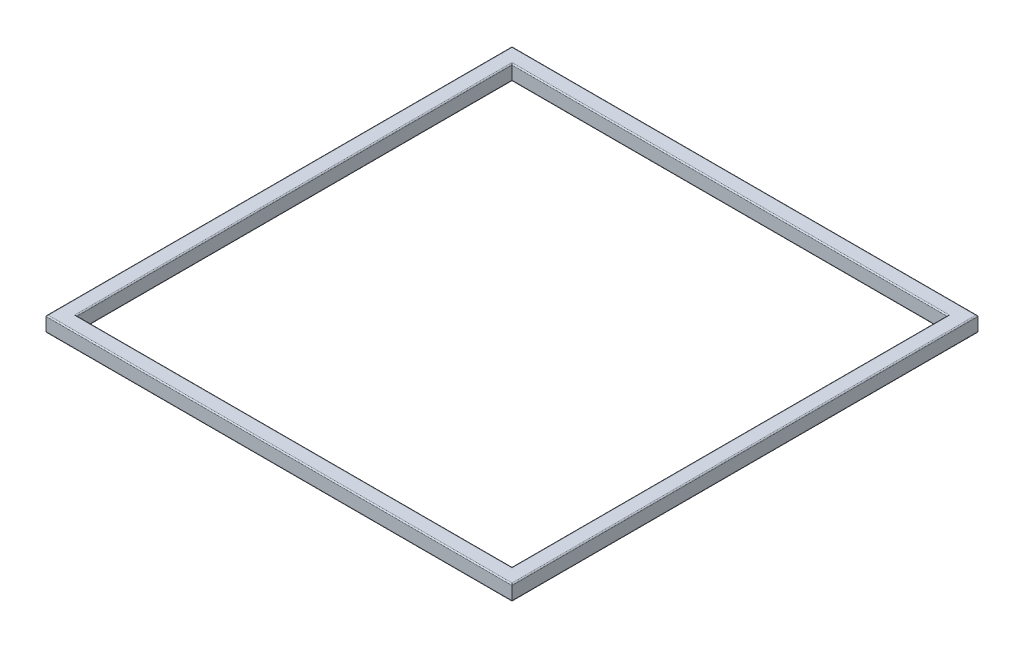
SolidWorks part; units mm, degrees
ref_plane "Front Plane" through (0, 0, 0) normal (0, 0, 1) x (1, 0, 0)
ref_plane "Top Plane" through (0, 0, 0) normal (0, 1, 0) x (1, 0, 0)
ref_plane "Right Plane" through (0, 0, 0) normal (1, 0, 0) x (0, 0, -1)
sketch "Sketch1" plane through (0, 0, 0) normal (0, 1, 0) x (1, 0, 0)
  line L1 (-610, 610) -> (610, 610)
  line L2 (-610, 610) -> (-610, -610)
  line L3 (-610, -610) -> (610, -610)
  line L4 (610, 610) -> (610, -610)
  line L5 (-610, 610) -> (610, -610) construction
  line L6 (-610, -610) -> (610, 610) construction
  line L7 (-570, -570) -> (570, -570)
  line L8 (-570, -570) -> (-570, 570)
  line L9 (-570, 570) -> (570, 570)
  line L10 (570, -570) -> (570, 570)
  line L11 (-570, -570) -> (570, 570) construction
  line L12 (-570, 570) -> (570, -570) construction
  point P0 (0, 0)
  point P6 (0, 0)
  dimension "D1" = 1220
  dimension "D2" = 40
extrude "Boss-Extrude1" add sketch "Sketch1" along normal blind 40
shell "Shell1" thickness 2
fillet "Fillet1" radius 3 16 edges at (0, 0, 570) (-570, 0, 0) (0, 0, -570) (570, 0, 0) (0, 0, -610) (-610, 0, 0) (0, 0, 610) (610, 0, 0) (-570, 40, 0) (0, 40, 570) (570, 40, 0) (0, 40, -570) (0, 40, 610) (-610, 40, 0) (0, 40, -610) (610, 40, 0)
